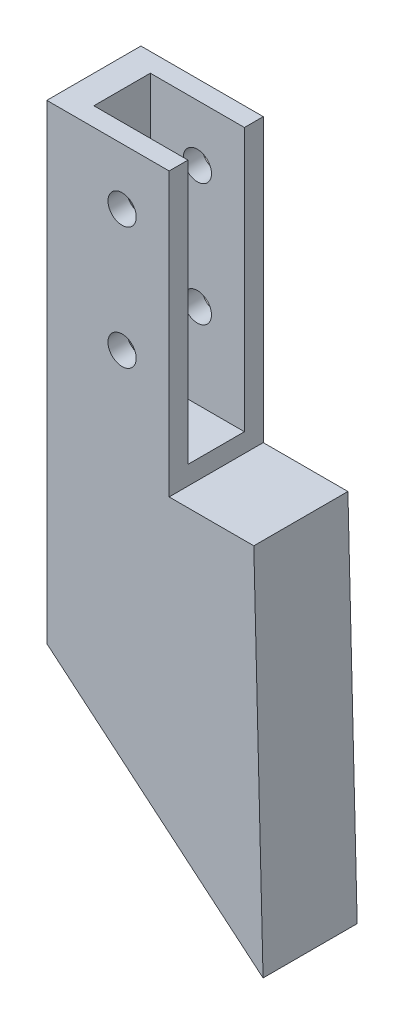
SolidWorks part; units mm, degrees
ref_plane "前视基准面" through (0, 0, 0) normal (0, 0, 1) x (1, 0, 0)
ref_plane "上视基准面" through (0, 0, 0) normal (0, 1, 0) x (1, 0, 0)
ref_plane "右视基准面" through (0, 0, 0) normal (1, 0, 0) x (0, 0, -1)
sketch "草图1" plane through (0, 0, 0) normal (0, 0, 1) x (1, 0, 0)
  line L0 (-6.5, -15) -> (-6.5, -35)
  line L1 (6.5, -15) -> (-6.5, -15)
  line L2 (6.5, -15) -> (6.5, 15)
  line L3 (6.5, 15) -> (-6.5, 15)
  line L4 (-6.5, -15) -> (-6.5, 15)
  line L5 (6.5, -15) -> (-6.5, 15) construction
  line L6 (6.5, 15) -> (-6.5, -15) construction
  line L7 (-6.5, -35) -> (16.4813, -54.2836)
  line L8 (16.4813, -54.2836) -> (15.4956, -15)
  line L9 (15.4956, -15) -> (6.5, -15)
  point P0 (0, 0)
  dimension "D1" = 30
  dimension "D2" = 20
  dimension "D3" = 13
  dimension "D4" = 130
  dimension "D5" = 30
extrude "凸台-拉伸1" add sketch "草图1" along normal blind 10 contours L4 L1 L2 L3 | L8 L9 L1 L0 L7 region at (5.9465, -30.4094, 0) region at (0, 0, 0)
sketch "草图2" plane through (6.5, 0, 0) normal (1, 0, 0) x (0, 0, -1)
  line L0 (-5, 15) -> (-5, -15) construction
  line L1 (-10, 15) -> (0, 15) construction
  line L2 (-10, -15) -> (0, -15) construction
  line L4 (-2, -13) -> (-8, -13)
  line L5 (-2, -13) -> (-2, 15)
  line L6 (-2, 15) -> (-8, 15)
  line L7 (-8, -13) -> (-8, 15)
  line L8 (-2, -13) -> (-8, 15) construction
  line L9 (-2, 15) -> (-8, -13) construction
  point P6 (-5, 1)
  dimension "D1" = 6
  dimension "D2" = 28
extrude "切除-拉伸1" cut sketch "草图2" against normal blind 10
sketch "草图3" plane through (0, 0, 10) normal (0, 0, 1) x (1, 0, 0)
  line L0 (6.5, 15) -> (1.5, 15) construction
  line L1 (6.5, 15) -> (-6.5, 15) construction
  line L2 (1.5, 15) -> (1.5, 9) construction
  circle A0 centre (1.5, 9) radius 1.5
  dimension "D3" = 3
  dimension "D1" = 5
  dimension "D2" = 6
extrude "切除-拉伸2" cut sketch "草图3" against normal through all
sketch "草图4" plane through (0, 0, 10) normal (0, 0, 1) x (1, 0, 0)
  line L0 (1.5, 9) -> (1.5, -4) construction
  circle A0 centre (1.5, -4) radius 1.5
  dimension "D1" = 3
  dimension "D2" = 13
extrude "切除-拉伸3" cut sketch "草图4" against normal through all
